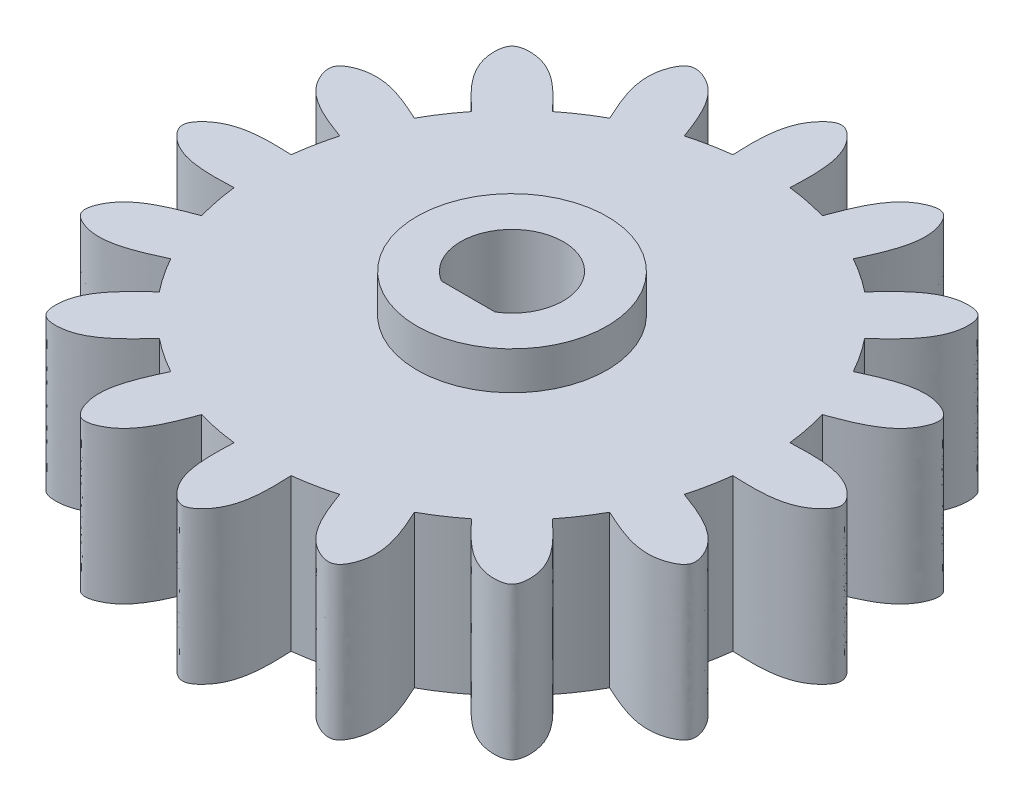
SolidWorks part; units mm, degrees
ref_plane "Front Plane" through (0, 0, 0) normal (0, 0, 1) x (1, 0, 0)
ref_plane "Top Plane" through (0, 0, 0) normal (0, 1, 0) x (1, 0, 0)
ref_plane "Right Plane" through (0, 0, 0) normal (1, 0, 0) x (0, 0, -1)
sketch "Sketch1" plane through (0, 0, 0) normal (0, 1, 0) x (1, 0, 0)
  line L0 (0, 0) -> (0, 10) construction
  circle A12 centre (0, 0) radius 13.2
  point P43 (0, 0)
  dimension "D1" = 26.4
extrude "Boss-Extrude1" add sketch "Sketch1" along normal blind 10
sketch "Sketch4" plane through (0, 0, 0) normal (0, -1, 0) x (1, 0, 0)
  line L0 (-1.5, -13.1145) -> (1.5, -13.1145)
  circle A1 centre (0, 0) radius 13.2 construction
  spline S0 degree 3 poles (1.5, -13.1145) (1.5223, -13.6797) (1.5744, -14.9965) (1.1993, -16.61) (0, -17.5178) (-1.1993, -16.61) (-1.5744, -14.9965) (-1.5223, -13.6797) (-1.5, -13.1145) knots 0 0 0 0 0.178316 0.415433 0.5 0.584567 0.821684 1 1 1 1
  dimension "D1" = 3
  dimension "D2" = 3
  dimension "D3" = 4.2143
  dimension "D4" = 1.4
  dimension "D5" = 0.4
  dimension "D6" = 0.7
  dimension "D7" = 1.7
sketch "Sketch2" plane through (0, 10, 0) normal (0, 1, 0) x (1, 0, 0)
  circle A0 centre (0, 0) radius 5
  dimension "D1" = 10
extrude "Boss-Extrude2" add sketch "Sketch2" along normal blind 2
extrude "Boss-Extrude5" add sketch "Sketch4" against normal blind 10
pattern_circular "CirPattern1" count 16 over 360 about axis through (0, 0, 0) along (0, 1, 0) of "Boss-Extrude5"
sketch "Sketch5" plane through (0, 12, 0) normal (0, 1, 0) x (1, 0, 0)
  line L0 (1.4142, -2.3) -> (-1.4142, -2.3)
  arc A0 (1.4142, -2.3) -> (-1.4142, -2.3) centre (0, 0) ccw
  point P5 (0, -2.3)
  dimension "D1" = 5.4
  dimension "D2" = 2.3
extrude "Cut-Extrude1" cut sketch "Sketch5" against normal through all contours A0 L0
sketch "Sketch6" plane through (0, 0, 0) normal (0, -1, 0) x (1, 0, 0)
  circle A2 centre (0, 0) radius 36.4787
extrude "Cut-Extrude2" cut sketch "Sketch6" against normal blind 2 contours A2
